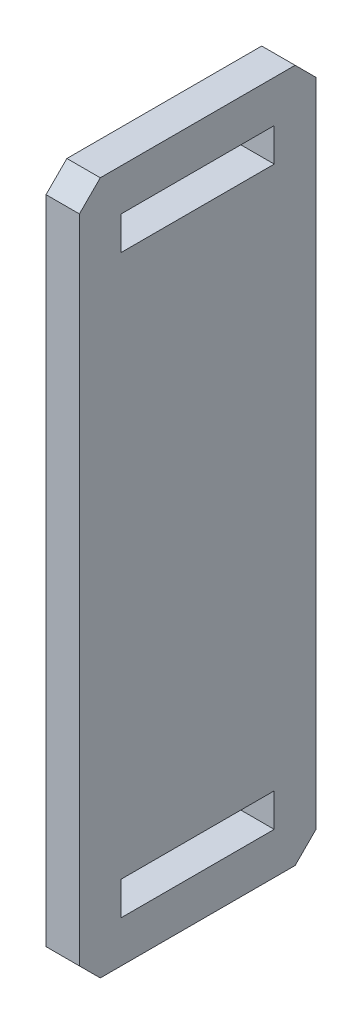
SolidWorks part; units mm, degrees
ref_plane "Front" through (0, 0, 0) normal (0, 0, 1) x (1, 0, 0)
ref_plane "Top" through (0, 0, 0) normal (0, 1, 0) x (1, 0, 0)
ref_plane "Right" through (0, 0, 0) normal (1, 0, 0) x (0, 0, -1)
ref_axis "side-side" through (80.9, 0, 0) along (-1, 0, 0)
ref_axis "up-down" through (0, 50, 0) along (0, -1, 0)
ref_axis "front-back" through (0, 0, -80.9) along (0, 0, 1)
sketch "Sketch1" plane through (0, 0, 0) normal (1, 0, 0) x (0, 0, -1)
  line L0 (-132.6173, 55.626) -> (-132.6173, 49.53) construction
  line L1 (-89.4373, 63.246) -> (-132.6173, 63.246)
  line L2 (-89.4373, 63.246) -> (-89.4373, -63.246)
  line L3 (-89.4373, -63.246) -> (-132.6173, -63.246)
  line L4 (-132.6173, 63.246) -> (-132.6173, -63.246)
  line L5 (-122.4573, 55.626) -> (-94.6424, 55.626) construction
  line L6 (-97.0573, -55.626) -> (-124.9973, -55.626) construction
  line L7 (-97.0573, 55.626) -> (-97.0573, 49.53) construction
  line L8 (-124.9973, -55.626) -> (-132.6173, -55.626) construction
  line L9 (-97.0573, 55.626) -> (-124.9973, 55.626)
  line L10 (-97.0573, 55.626) -> (-97.0573, 49.53)
  line L11 (-97.0573, 49.53) -> (-124.9973, 49.53)
  line L12 (-124.9973, 55.626) -> (-124.9973, 49.53)
  line L13 (-97.0573, -49.53) -> (-124.9973, -49.53)
  line L14 (-97.0573, -49.53) -> (-97.0573, -55.626)
  line L15 (-97.0573, -55.626) -> (-124.9973, -55.626)
  line L16 (-124.9973, -49.53) -> (-124.9973, -55.626)
  line L17 (-124.9973, -49.53) -> (-124.9973, -55.626) construction
  dimension "D1" = 7.62
  dimension "D2" = 7.62
  dimension "D3" = 7.62
extrude "Boss-Extrude1" add sketch "Sketch1" along normal mid plane 6.096
chamfer "Chamfer1" distance 3.81 angle 45 4 edges at (0, -63.246, 89.4373) (0, -63.246, 132.6173) (0, 63.246, 89.4373) (0, 63.246, 132.6173)
